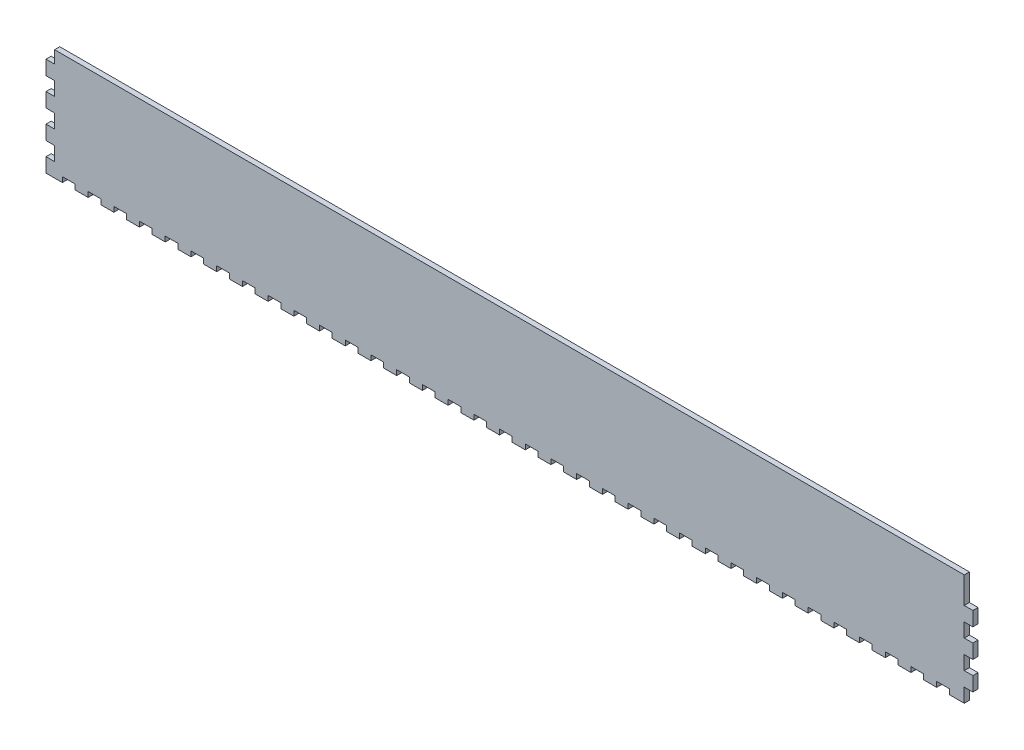
SolidWorks part; units mm, degrees
material "Perspex (TM) GS Acrylic Cast Sheet"
ref_plane "Front Plane" through (0, 0, 0) normal (0, 0, 1) x (1, 0, 0)
ref_plane "Top Plane" through (0, 0, 0) normal (0, 1, 0) x (1, 0, 0)
ref_plane "Right Plane" through (0, 0, 0) normal (1, 0, 0) x (0, 0, -1)
sketch "Sketch1" plane through (0, 0, 0) normal (0, 0, 1) x (1, 0, 0)
  line L0 (533.3602, 49.206) -> (533.3602, 64.6)
  line L413 (0, 0) -> (9.5185, 0)
  line L414 (9.5185, 3) -> (9.5185, 0)
  line L415 (9.5185, 3) -> (16.8869, 3)
  line L416 (16.8869, 3) -> (16.8869, 0)
  line L417 (16.8869, 0) -> (24.4554, 0)
  line L418 (24.4554, 3) -> (24.4554, 0)
  line L419 (24.4554, 3) -> (31.8238, 3)
  line L420 (31.8238, 3) -> (31.8238, 0)
  line L421 (31.8238, 0) -> (39.3923, 0)
  line L422 (39.3923, 3) -> (39.3923, 0)
  line L423 (39.3923, 3) -> (46.7607, 3)
  line L424 (46.7607, 3) -> (46.7607, 0)
  line L425 (46.7607, 0) -> (54.3292, 0)
  line L426 (54.3292, 3) -> (54.3292, 0)
  line L427 (54.3292, 3) -> (61.6976, 3)
  line L428 (61.6976, 3) -> (61.6976, 0)
  line L429 (61.6976, 0) -> (69.2661, 0)
  line L430 (69.2661, 3) -> (69.2661, 0)
  line L431 (69.2661, 3) -> (76.6345, 3)
  line L432 (76.6345, 3) -> (76.6345, 0)
  line L433 (76.6345, 0) -> (84.2031, 0)
  line L434 (84.2031, 3) -> (84.2031, 0)
  line L435 (84.2031, 3) -> (91.5713, 3)
  line L436 (91.5713, 3) -> (91.5713, 0)
  line L437 (91.5713, 0) -> (99.1398, 0)
  line L438 (99.1398, 3) -> (99.1398, 0)
  line L439 (99.1398, 3) -> (106.5082, 3)
  line L440 (106.5082, 3) -> (106.5082, 0)
  line L441 (106.5082, 0) -> (114.0767, 0)
  line L442 (114.0767, 3) -> (114.0767, 0)
  line L443 (114.0767, 3) -> (121.4452, 3)
  line L444 (121.4452, 3) -> (121.4452, 0)
  line L445 (121.4452, 0) -> (129.0137, 0)
  line L446 (129.0137, 3) -> (129.0137, 0)
  line L447 (129.0137, 3) -> (136.3822, 3)
  line L448 (136.3822, 3) -> (136.3822, 0)
  line L449 (136.3822, 0) -> (143.9507, 0)
  line L450 (143.9507, 3) -> (143.9507, 0)
  line L451 (143.9507, 3) -> (151.3191, 3)
  line L452 (151.3191, 3) -> (151.3191, 0)
  line L453 (151.3191, 0) -> (158.8876, 0)
  line L454 (158.8876, 3) -> (158.8876, 0)
  line L455 (158.8876, 3) -> (166.2561, 3)
  line L456 (166.2561, 3) -> (166.2561, 0)
  line L457 (166.2561, 0) -> (173.8242, 0)
  line L458 (173.8242, 3) -> (173.8242, 0)
  line L459 (173.8242, 3) -> (181.1927, 3)
  line L460 (181.1927, 3) -> (181.1927, 0)
  line L461 (181.1927, 0) -> (188.7612, 0)
  line L462 (188.7612, 3) -> (188.7612, 0)
  line L463 (188.7612, 3) -> (196.1297, 3)
  line L464 (196.1297, 3) -> (196.1297, 0)
  line L465 (196.1297, 0) -> (203.6981, 0)
  line L466 (203.6981, 3) -> (203.6981, 0)
  line L467 (203.6981, 3) -> (211.0666, 3)
  line L468 (211.0666, 3) -> (211.0666, 0)
  line L469 (211.0666, 0) -> (218.6351, 0)
  line L470 (218.6351, 3) -> (218.6351, 0)
  line L471 (218.6351, 3) -> (226.0036, 3)
  line L472 (226.0036, 3) -> (226.0036, 0)
  line L473 (226.0036, 0) -> (233.5721, 0)
  line L474 (233.5721, 3) -> (233.5721, 0)
  line L475 (233.5721, 3) -> (240.9406, 3)
  line L476 (240.9406, 3) -> (240.9406, 0)
  line L477 (240.9406, 0) -> (248.5091, 0)
  line L478 (248.5091, 3) -> (248.5091, 0)
  line L479 (248.5091, 3) -> (255.8775, 3)
  line L480 (255.8775, 3) -> (255.8775, 0)
  line L481 (255.8775, 0) -> (263.4457, 0)
  line L482 (263.4457, 3) -> (263.4457, 0)
  line L483 (263.4457, 3) -> (270.8141, 3)
  line L484 (270.8141, 3) -> (270.8141, 0)
  line L485 (270.8141, 0) -> (278.3826, 0)
  line L486 (278.3826, 3) -> (278.3826, 0)
  line L487 (278.3826, 3) -> (285.7511, 3)
  line L488 (285.7511, 3) -> (285.7511, 0)
  line L489 (285.7511, 0) -> (293.3196, 0)
  line L490 (293.3196, 3) -> (293.3196, 0)
  line L491 (293.3196, 3) -> (300.688, 3)
  line L492 (300.688, 3) -> (300.688, 0)
  line L493 (300.688, 0) -> (308.2565, 0)
  line L494 (308.2565, 3) -> (308.2565, 0)
  line L495 (308.2565, 3) -> (315.625, 3)
  line L496 (315.625, 3) -> (315.625, 0)
  line L497 (315.625, 0) -> (323.1935, 0)
  line L498 (323.1935, 3) -> (323.1935, 0)
  line L499 (323.1935, 3) -> (330.562, 3)
  line L500 (330.562, 3) -> (330.562, 0)
  line L501 (330.562, 0) -> (338.1301, 0)
  line L502 (338.1301, 3) -> (338.1301, 0)
  line L503 (338.1301, 3) -> (345.4986, 3)
  line L504 (345.4986, 3) -> (345.4986, 0)
  line L505 (345.4986, 0) -> (353.0671, 0)
  line L506 (353.0671, 3) -> (353.0671, 0)
  line L507 (353.0671, 3) -> (360.4356, 3)
  line L508 (360.4356, 3) -> (360.4356, 0)
  line L509 (360.4356, 0) -> (368.0041, 0)
  line L510 (368.0041, 3) -> (368.0041, 0)
  line L511 (368.0041, 3) -> (375.3725, 3)
  line L512 (375.3725, 3) -> (375.3725, 0)
  line L513 (375.3725, 0) -> (382.941, 0)
  line L514 (382.941, 3) -> (382.941, 0)
  line L515 (382.941, 3) -> (390.3095, 3)
  line L516 (390.3095, 3) -> (390.3095, 0)
  line L517 (390.3095, 0) -> (397.878, 0)
  line L518 (397.878, 3) -> (397.878, 0)
  line L519 (397.878, 3) -> (405.2464, 3)
  line L520 (405.2464, 3) -> (405.2464, 0)
  line L521 (405.2464, 0) -> (412.8149, 0)
  line L522 (412.8149, 3) -> (412.8149, 0)
  line L523 (412.8149, 3) -> (420.1834, 3)
  line L524 (420.1834, 3) -> (420.1834, 0)
  line L525 (420.1834, 0) -> (427.7515, 0)
  line L526 (427.7515, 3) -> (427.7515, 0)
  line L527 (427.7515, 3) -> (435.12, 3)
  line L528 (435.12, 3) -> (435.12, 0)
  line L529 (435.12, 0) -> (442.6885, 0)
  line L530 (442.6885, 3) -> (442.6885, 0)
  line L531 (442.6885, 3) -> (450.057, 3)
  line L532 (450.057, 3) -> (450.057, 0)
  line L533 (450.057, 0) -> (457.6255, 0)
  line L534 (457.6255, 3) -> (457.6255, 0)
  line L535 (457.6255, 3) -> (464.994, 3)
  line L536 (464.994, 3) -> (464.994, 0)
  line L537 (464.994, 0) -> (472.5625, 0)
  line L538 (472.5625, 3) -> (472.5625, 0)
  line L539 (472.5625, 3) -> (479.9309, 3)
  line L540 (479.9309, 3) -> (479.9309, 0)
  line L541 (479.9309, 0) -> (487.4994, 0)
  line L542 (487.4994, 3) -> (487.4994, 0)
  line L543 (487.4994, 3) -> (494.8679, 3)
  line L544 (494.8679, 3) -> (494.8679, 0)
  line L545 (494.8679, 0) -> (502.4364, 0)
  line L546 (502.4364, 3) -> (502.4364, 0)
  line L547 (502.4364, 3) -> (509.8045, 3)
  line L548 (509.8045, 3) -> (509.8045, 0)
  line L549 (509.8045, 0) -> (517.373, 0)
  line L550 (517.373, 3) -> (517.373, 0)
  line L551 (517.373, 3) -> (524.7414, 3)
  line L552 (524.7414, 3) -> (524.7414, 0)
  line L553 (524.7414, 0) -> (533.3602, 0)
  line L554 (0, 0) -> (0, 8.3)
  line L555 (5, 8.3) -> (0, 8.3)
  line L556 (5, 8.3) -> (5, 16.38)
  line L557 (5, 16.38) -> (0, 16.38)
  line L558 (0, 16.38) -> (0, 24.68)
  line L559 (5, 24.68) -> (0, 24.68)
  line L560 (5, 24.68) -> (5, 32.76)
  line L561 (5, 32.76) -> (0, 32.76)
  line L562 (0, 32.76) -> (0, 41.06)
  line L563 (533.3602, 0) -> (533.3602, 8.1458)
  line L564 (538.3599, 8.1458) -> (533.3602, 8.1458)
  line L565 (538.3599, 8.1458) -> (538.3599, 16.4351)
  line L566 (538.3599, 16.4351) -> (533.3602, 16.4351)
  line L567 (533.3602, 16.4351) -> (533.3602, 24.5243)
  line L568 (538.3599, 24.5243) -> (533.3602, 24.5243)
  line L569 (538.3599, 24.5243) -> (538.3599, 32.8136)
  line L570 (538.3599, 32.8136) -> (533.3602, 32.8136)
  line L571 (533.3602, 32.8136) -> (533.3602, 40.9167)
  line L572 (533.3602, 64.6) -> (5, 64.6)
  line L573 (5, 41.06) -> (0, 41.06)
  line L574 (5, 41.06) -> (5, 49.0343)
  line L575 (5, 49.0343) -> (0, 49.0343)
  line L576 (0, 49.0343) -> (0, 57.3343)
  line L577 (5, 57.3343) -> (0, 57.3343)
  line L578 (5, 57.3343) -> (5, 64.6)
  line L579 (538.3599, 40.9167) -> (533.3602, 40.9167)
  line L580 (538.3599, 40.9167) -> (538.3599, 49.206)
  line L581 (538.3599, 49.206) -> (533.3602, 49.206)
  dimension "D1" = 64.6
  dimension "D2" = 7.2657
  dimension "D3" = 8.3
  dimension "D4" = 8.08
  dimension "D5" = 8.08
extrude "Boss-Extrude1" add sketch "Sketch1" along normal blind 3
sketch "Sketch2" [suppressed] plane through (0, 0, 3) normal (0, 0, 1) x (1, 0, 0)
  line L1 (155.1929, 42.1264) -> (155.1929, 45.3454)
  line L2 (153.3481, 41.1853) -> (155.1929, 42.1264)
  line L3 (151.5033, 40.2441) -> (153.3481, 41.1853)
  line L4 (151.5033, 44.4043) -> (151.5033, 40.2441)
  line L5 (151.5033, 48.5644) -> (151.5033, 44.4043)
  line L6 (153.3481, 48.5644) -> (151.5033, 48.5644)
  line L7 (155.1929, 48.5644) -> (153.3481, 48.5644)
  line L8 (155.1929, 45.3454) -> (155.1929, 48.5644)
  line L9 (149.6585, 37.4854) -> (149.6585, 43.9473)
  line L10 (153.3481, 39.3405) -> (149.6585, 37.4854)
  line L11 (157.0377, 41.1956) -> (153.3481, 39.3405)
  line L12 (157.0377, 45.8024) -> (157.0377, 41.1956)
  line L13 (157.0377, 50.4092) -> (157.0377, 45.8024)
  line L14 (153.3481, 50.4092) -> (157.0377, 50.4092)
  line L15 (149.6585, 50.4092) -> (153.3481, 50.4092)
  line L16 (149.6585, 43.9473) -> (149.6585, 50.4092)
  line L17 (108.6121, 36.5921) -> (108.6121, 42.5782)
  line L18 (106.7673, 35.6509) -> (108.6121, 36.5921)
  line L19 (104.9225, 34.7098) -> (106.7673, 35.6509)
  line L20 (104.9225, 41.6371) -> (104.9225, 34.7098)
  line L21 (104.9225, 48.5644) -> (104.9225, 41.6371)
  line L22 (106.7673, 48.5644) -> (104.9225, 48.5644)
  line L23 (108.6121, 48.5644) -> (106.7673, 48.5644)
  line L24 (108.6121, 42.5782) -> (108.6121, 48.5644)
  line L25 (110.4569, 35.7343) -> (107.0196, 33.8478)
  line L26 (110.4569, 43.0717) -> (110.4569, 35.7343)
  line L27 (110.4569, 50.4092) -> (110.4569, 43.0717)
  line L28 (106.7673, 50.4092) -> (110.4569, 50.4092)
  line L29 (103.0777, 50.4092) -> (106.7673, 50.4092)
  line L30 (103.0777, 41.1853) -> (103.0777, 50.4092)
  line L31 (396.8595, 27.8106) -> (396.8595, 38.1875)
  line L32 (395.0147, 27.8106) -> (396.8595, 27.8106)
  line L33 (393.1699, 27.8106) -> (395.0147, 27.8106)
  line L34 (393.1699, 38.1875) -> (393.1699, 27.8106)
  line L35 (393.1699, 48.5644) -> (393.1699, 38.1875)
  line L36 (395.0147, 48.5644) -> (393.1699, 48.5644)
  line L37 (396.8595, 48.5644) -> (395.0147, 48.5644)
  line L38 (396.8595, 38.1875) -> (396.8595, 48.5644)
  line L39 (391.3251, 25.9658) -> (391.3251, 38.1875)
  line L40 (395.0147, 25.9658) -> (391.3251, 25.9658)
  line L41 (398.7042, 25.9658) -> (395.0147, 25.9658)
  line L42 (398.7042, 38.1875) -> (398.7042, 25.9658)
  line L43 (398.7042, 50.4092) -> (398.7042, 38.1875)
  line L44 (395.0147, 50.4092) -> (398.7042, 50.4092)
  line L45 (391.3251, 50.4092) -> (395.0147, 50.4092)
  line L46 (391.3251, 38.1875) -> (391.3251, 50.4092)
  line L47 (356.7354, 27.8106) -> (356.7354, 38.1875)
  line L48 (354.8907, 27.8106) -> (356.7354, 27.8106)
  line L49 (353.0459, 27.8106) -> (354.8907, 27.8106)
  line L50 (353.0459, 38.1875) -> (353.0459, 27.8106)
  line L51 (353.0459, 48.5644) -> (353.0459, 38.1875)
  line L52 (354.8907, 48.5644) -> (353.0459, 48.5644)
  line L53 (356.7354, 48.5644) -> (354.8907, 48.5644)
  line L54 (356.7354, 38.1875) -> (356.7354, 48.5644)
  line L55 (351.2011, 25.9658) -> (351.2011, 38.1875)
  line L56 (354.8907, 25.9658) -> (351.2011, 25.9658)
  line L57 (358.5802, 25.9658) -> (354.8907, 25.9658)
  line L58 (358.5802, 38.1875) -> (358.5802, 25.9658)
  line L59 (358.5802, 50.4092) -> (358.5802, 38.1875)
  line L60 (354.8907, 50.4092) -> (358.5802, 50.4092)
  line L61 (351.2011, 50.4092) -> (354.8907, 50.4092)
  line L62 (351.2011, 38.1875) -> (351.2011, 50.4092)
  line L63 (149.6585, 25.9658) -> (149.6585, 29.6605)
  line L64 (153.3481, 25.9658) -> (149.6585, 25.9658)
  line L65 (157.0377, 25.9658) -> (153.3481, 25.9658)
  line L66 (157.0377, 27.8054) -> (157.0377, 25.9658)
  line L67 (149.6585, 33.3552) -> (153.3481, 31.5002)
  line L68 (149.6585, 29.6605) -> (149.6585, 33.3552)
  line L69 (235.7413, 17.4806) -> (235.7411, 17.4806)
  line L70 (237.3694, 50.4092) -> (237.2123, 32.6759)
  line L71 (234.5605, 50.4092) -> (237.3694, 50.4092)
  line L72 (231.7515, 50.4092) -> (234.5605, 50.4092)
  line L73 (231.7515, 52.254) -> (231.7515, 50.4092)
  line L74 (231.7515, 54.0988) -> (231.7515, 52.254)
  line L75 (239.1306, 54.0988) -> (231.7515, 54.0988)
  line L76 (246.5098, 54.0988) -> (239.1306, 54.0988)
  line L77 (246.5098, 52.254) -> (246.5098, 54.0988)
  line L78 (246.5098, 50.4092) -> (246.5098, 52.254)
  line L79 (243.6972, 50.4092) -> (246.5098, 50.4092)
  line L80 (240.8845, 50.4092) -> (243.6972, 50.4092)
  line L81 (241.0453, 32.676) -> (240.8845, 50.4092)
  line L82 (242.8201, 48.5644) -> (242.817, 34.3826)
  line L83 (245.5873, 48.5644) -> (242.8201, 48.5644)
  line L84 (248.3544, 48.5644) -> (245.5873, 48.5644)
  line L85 (248.3544, 52.254) -> (248.3544, 48.5644)
  line L86 (248.3544, 55.9435) -> (248.3544, 52.254)
  line L87 (239.1305, 55.9435) -> (248.3544, 55.9435)
  line L88 (229.9066, 55.9435) -> (239.1305, 55.9435)
  line L89 (229.9066, 52.254) -> (229.9066, 55.9435)
  line L90 (229.9066, 48.5644) -> (229.9066, 52.254)
  line L91 (232.6738, 48.5644) -> (229.9066, 48.5644)
  line L92 (235.4409, 48.5644) -> (232.6738, 48.5644)
  line L93 (235.4409, 34.7981) -> (235.4409, 48.5644)
  line L94 (108.5361, 23.064) -> (106.9443, 23.8231)
  line L95 (108.8601, 18.743) -> (108.5361, 23.064)
  line L96 (103.0777, 27.8734) -> (106.7669, 25.8819)
  line L97 (103.0777, 24.4526) -> (103.0777, 27.8734)
  line L98 (99.4734, 54.0988) -> (99.2858, 34.8438)
  line L99 (106.8099, 54.0988) -> (99.4734, 54.0988)
  line L100 (114.1464, 54.0988) -> (106.8099, 54.0988)
  line L101 (114.1464, 43.5902) -> (114.1464, 54.0988)
  line L102 (114.1464, 33.0817) -> (114.1464, 43.5902)
  line L103 (111.0943, 31.5766) -> (114.1464, 33.0817)
  line L104 (113.9159, 26.6576) -> (111.2929, 28.0508)
  line L105 (114.2545, 21.5845) -> (113.9159, 26.6576)
  line L106 (115.9912, 27.6268) -> (115.9456, 22.9914)
  line L107 (113.8021, 28.6904) -> (115.9912, 27.6268)
  line L108 (111.613, 29.7539) -> (113.8021, 28.6904)
  line L109 (113.8021, 30.8665) -> (111.613, 29.7539)
  line L110 (115.9912, 31.979) -> (113.8021, 30.8665)
  line L111 (115.9912, 43.9613) -> (115.9912, 31.979)
  line L112 (115.9912, 55.9435) -> (115.9912, 43.9613)
  line L113 (106.7673, 55.9435) -> (115.9912, 55.9435)
  line L114 (97.5434, 55.9435) -> (106.7673, 55.9435)
  line L115 (97.5434, 38.2571) -> (97.5434, 55.9435)
  line L116 (333.9811, 16.5113) -> (333.9812, 16.5113)
  line L117 (329.7555, 31.7308) -> (329.4691, 24.8128)
  line L118 (331.6999, 25.9658) -> (329.7555, 31.7308)
  line L119 (317.0725, 55.9435) -> (317.0269, 36.6886)
  line L120 (313.383, 55.9435) -> (317.0725, 55.9435)
  line L121 (309.6934, 55.9435) -> (313.383, 55.9435)
  line L122 (309.6934, 44.6442) -> (309.6934, 55.9435)
  line L123 (309.6934, 33.345) -> (309.6934, 44.6442)
  line L124 (307.8486, 33.345) -> (309.6934, 33.345)
  line L125 (306.0038, 33.345) -> (307.8486, 33.345)
  line L126 (306.0038, 44.6442) -> (306.0038, 33.345)
  line L127 (306.0038, 55.9435) -> (306.0038, 44.6442)
  line L128 (302.3143, 55.9435) -> (306.0038, 55.9435)
  line L129 (298.6247, 55.9435) -> (302.3143, 55.9435)
  line L130 (298.6275, 38.5334) -> (298.6247, 55.9435)
  line L131 (300.5485, 54.0988) -> (300.3487, 35.0744)
  line L132 (302.3538, 54.0988) -> (300.5485, 54.0988)
  line L133 (304.1591, 54.0988) -> (302.3538, 54.0988)
  line L134 (304.1591, 42.7995) -> (304.1591, 54.0988)
  line L135 (304.1591, 31.5002) -> (304.1591, 42.7995)
  line L136 (307.8487, 31.5002) -> (304.1591, 31.5002)
  line L137 (311.5382, 31.5002) -> (307.8487, 31.5002)
  line L138 (311.5382, 42.7995) -> (311.5382, 31.5002)
  line L139 (311.5382, 54.0988) -> (311.5382, 42.7995)
  line L140 (313.3379, 54.0988) -> (311.5382, 54.0988)
  line L141 (315.1375, 54.0988) -> (313.3379, 54.0988)
  line L142 (315.3524, 34.3826) -> (315.1375, 54.0988)
  line L143 (427.7596, 38.8793) -> (427.714, 27.2341)
  line L144 (424.07, 38.8793) -> (427.7596, 38.8793)
  line L145 (420.3805, 38.8793) -> (424.07, 38.8793)
  line L146 (420.3805, 33.345) -> (420.3805, 38.8793)
  line L147 (420.3805, 27.8106) -> (420.3805, 33.345)
  line L148 (418.5357, 27.8106) -> (420.3805, 27.8106)
  line L149 (416.6909, 27.8106) -> (418.5357, 27.8106)
  line L150 (416.6909, 38.1875) -> (416.6909, 27.8106)
  line L151 (416.6909, 48.5644) -> (416.6909, 38.1875)
  line L152 (418.5357, 48.5644) -> (416.6909, 48.5644)
  line L153 (420.3805, 48.5644) -> (418.5357, 48.5644)
  line L154 (420.3805, 45.7972) -> (420.3805, 48.5644)
  line L155 (420.3805, 43.0301) -> (420.3805, 45.7972)
  line L156 (424.07, 43.0301) -> (420.3805, 43.0301)
  line L157 (427.7596, 43.0301) -> (424.07, 43.0301)
  line L158 (427.7596, 49.4868) -> (427.7596, 43.0301)
  line L159 (427.7596, 55.9435) -> (427.7596, 49.4868)
  line L160 (418.5357, 55.9435) -> (427.7596, 55.9435)
  line L161 (409.3118, 55.9435) -> (418.5357, 55.9435)
  line L162 (409.3118, 38.7183) -> (409.3118, 55.9435)
  line L163 (411.2363, 54.0988) -> (411.0551, 35.305)
  line L164 (418.5755, 54.0988) -> (411.2363, 54.0988)
  line L165 (425.9148, 54.0988) -> (418.5755, 54.0988)
  line L166 (425.9148, 49.4868) -> (425.9148, 54.0988)
  line L167 (425.9148, 44.8748) -> (425.9148, 49.4868)
  line L168 (424.07, 44.8748) -> (425.9148, 44.8748)
  line L169 (422.2252, 44.8748) -> (424.07, 44.8748)
  line L170 (422.2252, 47.642) -> (422.2252, 44.8748)
  line L171 (422.2252, 50.4092) -> (422.2252, 47.642)
  line L172 (418.5357, 50.4092) -> (422.2252, 50.4092)
  line L173 (414.8461, 50.4092) -> (418.5357, 50.4092)
  line L174 (414.8461, 38.1875) -> (414.8461, 50.4092)
  line L175 (414.8461, 25.9658) -> (414.8461, 38.1875)
  line L176 (418.5357, 25.9658) -> (414.8461, 25.9658)
  line L177 (422.2252, 25.9658) -> (418.5357, 25.9658)
  line L178 (422.2252, 31.5002) -> (422.2252, 25.9658)
  line L179 (422.2252, 37.0345) -> (422.2252, 31.5002)
  line L180 (424.0113, 37.0345) -> (422.2252, 37.0345)
  line L181 (425.7975, 37.0345) -> (424.0113, 37.0345)
  line L182 (426.0611, 25.1587) -> (425.7975, 37.0345)
  line L183 (369.4931, 13.7313) -> (369.493, 13.7313)
  line L184 (371.1129, 54.0988) -> (370.9311, 33.2296)
  line L185 (372.9175, 54.0988) -> (371.1129, 54.0988)
  line L186 (374.7222, 54.0988) -> (372.9175, 54.0988)
  line L187 (374.7222, 40.0323) -> (374.7222, 54.0988)
  line L188 (374.7222, 25.9658) -> (374.7222, 40.0323)
  line L189 (377.4237, 25.9658) -> (374.7222, 25.9658)
  line L190 (380.1253, 25.9658) -> (377.4237, 25.9658)
  line L191 (380.4506, 20.7774) -> (380.1253, 25.9658)
  line L192 (382.1012, 27.8106) -> (382.0981, 24.4669)
  line L193 (379.334, 27.8106) -> (382.1012, 27.8106)
  line L194 (376.5668, 27.8106) -> (379.334, 27.8106)
  line L195 (376.5668, 41.8771) -> (376.5668, 27.8106)
  line L196 (376.5668, 55.9435) -> (376.5668, 41.8771)
  line L197 (372.8773, 55.9435) -> (376.5668, 55.9435)
  line L198 (369.1877, 55.9435) -> (372.8773, 55.9435)
  line L199 (369.1877, 36.6429) -> (369.1877, 55.9435)
  line L200 (294.0128, 33.345) -> (293.9672, 24.2363)
  line L201 (290.3232, 33.345) -> (294.0128, 33.345)
  line L202 (286.6337, 33.345) -> (290.3232, 33.345)
  line L203 (286.6337, 30.5778) -> (286.6337, 33.345)
  line L204 (286.6337, 27.8106) -> (286.6337, 30.5778)
  line L205 (284.7889, 27.8106) -> (286.6337, 27.8106)
  line L206 (282.9441, 27.8106) -> (284.7889, 27.8106)
  line L207 (282.9441, 38.1875) -> (282.9441, 27.8106)
  line L208 (282.9441, 48.5644) -> (282.9441, 38.1875)
  line L209 (284.7889, 48.5644) -> (282.9441, 48.5644)
  line L210 (286.6337, 48.5644) -> (284.7889, 48.5644)
  line L211 (286.6337, 45.7972) -> (286.6337, 48.5644)
  line L212 (286.6337, 43.0301) -> (286.6337, 45.7972)
  line L213 (290.3232, 43.0301) -> (286.6337, 43.0301)
  line L214 (294.0128, 43.0301) -> (290.3232, 43.0301)
  line L215 (294.0128, 49.4868) -> (294.0128, 43.0301)
  line L216 (294.0128, 55.9435) -> (294.0128, 49.4868)
  line L217 (284.7889, 55.9435) -> (294.0128, 55.9435)
  line L218 (275.565, 55.9435) -> (284.7889, 55.9435)
  line L219 (275.565, 38.4877) -> (275.565, 55.9435)
  line L220 (277.4958, 54.0988) -> (277.3072, 35.0744)
  line L221 (284.8319, 54.0988) -> (277.4958, 54.0988)
  line L222 (292.168, 54.0988) -> (284.8319, 54.0988)
  line L223 (292.168, 49.4868) -> (292.168, 54.0988)
  line L224 (292.168, 44.8748) -> (292.168, 49.4868)
  line L225 (290.3232, 44.8748) -> (292.168, 44.8748)
  line L226 (288.4785, 44.8748) -> (290.3232, 44.8748)
  line L227 (288.4785, 47.642) -> (288.4785, 44.8748)
  line L228 (288.4785, 50.4092) -> (288.4785, 47.642)
  line L229 (284.7889, 50.4092) -> (288.4785, 50.4092)
  line L230 (281.0993, 50.4092) -> (284.7889, 50.4092)
  line L231 (281.0993, 38.1875) -> (281.0993, 50.4092)
  line L232 (281.0993, 25.9658) -> (281.0993, 38.1875)
  line L233 (284.7889, 25.9658) -> (281.0993, 25.9658)
  line L234 (288.4785, 25.9658) -> (284.7889, 25.9658)
  line L235 (288.4785, 28.733) -> (288.4785, 25.9658)
  line L236 (288.4785, 31.5002) -> (288.4785, 28.733)
  line L237 (290.2572, 31.5002) -> (288.4785, 31.5002)
  line L238 (292.036, 31.5002) -> (290.2572, 31.5002)
  line L239 (292.321, 22.1609) -> (292.036, 31.5002)
  line L240 (191.0103, 13.7313) -> (191.0102, 13.7313)
  line L241 (192.6301, 54.0988) -> (192.4483, 33.2296)
  line L242 (194.4348, 54.0988) -> (192.6301, 54.0988)
  line L243 (196.2394, 54.0988) -> (194.4348, 54.0988)
  line L244 (196.2394, 40.0323) -> (196.2394, 54.0988)
  line L245 (196.2394, 25.9658) -> (196.2394, 40.0323)
  line L246 (198.9409, 25.9658) -> (196.2394, 25.9658)
  line L247 (201.6425, 25.9658) -> (198.9409, 25.9658)
  line L248 (201.9678, 20.7774) -> (201.6425, 25.9658)
  line L249 (203.6184, 27.8106) -> (203.6153, 24.4669)
  line L250 (200.8513, 27.8106) -> (203.6184, 27.8106)
  line L251 (198.0841, 27.8106) -> (200.8513, 27.8106)
  line L252 (198.0841, 41.8771) -> (198.0841, 27.8106)
  line L253 (198.0841, 55.9435) -> (198.0841, 41.8771)
  line L254 (194.3945, 55.9435) -> (198.0841, 55.9435)
  line L255 (190.7049, 55.9435) -> (194.3945, 55.9435)
  line L256 (190.7049, 36.6429) -> (190.7049, 55.9435)
  line L257 (146.0492, 54.0988) -> (145.8674, 33.2296)
  line L258 (153.3882, 54.0988) -> (146.0492, 54.0988)
  line L259 (160.7272, 54.0988) -> (153.3882, 54.0988)
  line L260 (160.7272, 46.3574) -> (160.7272, 54.0988)
  line L261 (160.7272, 38.6161) -> (160.7272, 46.3574)
  line L262 (157.6751, 37.111) -> (160.7272, 38.6161)
  line L263 (160.4966, 32.192) -> (157.8736, 33.5851)
  line L264 (160.7824, 24.5738) -> (160.4966, 32.192)
  line L265 (162.572, 33.1611) -> (162.5264, 25.9892)
  line L266 (160.396, 34.2183) -> (162.572, 33.1611)
  line L267 (158.22, 35.2755) -> (160.396, 34.2183)
  line L268 (160.0501, 36.3833) -> (158.22, 35.2755)
  line L269 (162.572, 55.9435) -> (162.572, 46.7196)
  line L270 (153.3481, 55.9435) -> (162.572, 55.9435)
  line L271 (144.1242, 55.9435) -> (153.3481, 55.9435)
  line L272 (144.1242, 36.6429) -> (144.1242, 55.9435)
  line L273 (270.953, 27.8106) -> (270.9074, 21.2386)
  line L274 (265.4187, 27.8106) -> (270.953, 27.8106)
  line L275 (259.8843, 27.8106) -> (265.4187, 27.8106)
  line L276 (259.8843, 29.6554) -> (259.8843, 27.8106)
  line L277 (259.8843, 31.5002) -> (259.8843, 29.6554)
  line L278 (265.4187, 31.5002) -> (259.8843, 31.5002)
  line L279 (270.953, 31.5002) -> (265.4187, 31.5002)
  line L280 (270.953, 35.1897) -> (270.953, 31.5002)
  line L281 (270.953, 38.8793) -> (270.953, 35.1897)
  line L282 (265.4187, 38.8793) -> (270.953, 38.8793)
  line L283 (259.8843, 38.8793) -> (265.4187, 38.8793)
  line L284 (259.8843, 43.7218) -> (259.8843, 38.8793)
  line L285 (259.8843, 48.5644) -> (259.8843, 43.7218)
  line L286 (261.7291, 48.5644) -> (259.8843, 48.5644)
  line L287 (263.5739, 48.5644) -> (261.7291, 48.5644)
  line L288 (263.5739, 45.7972) -> (263.5739, 48.5644)
  line L289 (263.5739, 43.0301) -> (263.5739, 45.7972)
  line L290 (267.2634, 43.0301) -> (263.5739, 43.0301)
  line L291 (270.953, 43.0301) -> (267.2634, 43.0301)
  line L292 (270.953, 49.4868) -> (270.953, 43.0301)
  line L293 (270.953, 55.9435) -> (270.953, 49.4868)
  line L294 (261.7291, 55.9435) -> (270.953, 55.9435)
  line L295 (252.5052, 55.9435) -> (261.7291, 55.9435)
  line L296 (252.5052, 37.7959) -> (252.5052, 55.9435)
  line L297 (254.4337, 54.0988) -> (254.2478, 34.3826)
  line L298 (261.771, 54.0988) -> (254.4337, 54.0988)
  line L299 (269.1082, 54.0988) -> (261.771, 54.0988)
  line L300 (269.1082, 49.4868) -> (269.1082, 54.0988)
  line L301 (269.1082, 44.8748) -> (269.1082, 49.4868)
  line L302 (267.2634, 44.8748) -> (269.1082, 44.8748)
  line L303 (265.4187, 44.8748) -> (267.2634, 44.8748)
  line L304 (265.4187, 47.642) -> (265.4187, 44.8748)
  line L305 (265.4187, 50.4092) -> (265.4187, 47.642)
  line L306 (261.7291, 50.4092) -> (265.4187, 50.4092)
  line L307 (258.0395, 50.4092) -> (261.7291, 50.4092)
  line L308 (258.0395, 43.7218) -> (258.0395, 50.4092)
  line L309 (258.0395, 37.0345) -> (258.0395, 43.7218)
  line L310 (263.5739, 37.0345) -> (258.0395, 37.0345)
  line L311 (269.1082, 37.0345) -> (263.5739, 37.0345)
  line L312 (269.1082, 35.1897) -> (269.1082, 37.0345)
  line L313 (269.1082, 33.345) -> (269.1082, 35.1897)
  line L314 (263.5739, 33.345) -> (269.1082, 33.345)
  line L315 (258.0395, 33.345) -> (263.5739, 33.345)
  line L316 (258.0395, 29.6554) -> (258.0395, 33.345)
  line L317 (258.0395, 25.9658) -> (258.0395, 29.6554)
  line L318 (263.5022, 25.9658) -> (258.0395, 25.9658)
  line L319 (268.9648, 25.9658) -> (263.5022, 25.9658)
  line L320 (269.276, 19.1632) -> (268.9648, 25.9658)
  line L321 (186.093, 27.8106) -> (186.0474, 21.2386)
  line L322 (180.5586, 27.8106) -> (186.093, 27.8106)
  line L323 (175.0243, 27.8106) -> (180.5586, 27.8106)
  line L324 (175.0243, 29.6554) -> (175.0243, 27.8106)
  line L325 (175.0243, 31.5002) -> (175.0243, 29.6554)
  line L326 (180.5586, 31.5002) -> (175.0243, 31.5002)
  line L327 (186.093, 31.5002) -> (180.5586, 31.5002)
  line L328 (186.093, 35.1897) -> (186.093, 31.5002)
  line L329 (186.093, 38.8793) -> (186.093, 35.1897)
  line L330 (180.5586, 38.8793) -> (186.093, 38.8793)
  line L331 (175.0243, 38.8793) -> (180.5586, 38.8793)
  line L332 (175.0243, 43.7218) -> (175.0243, 38.8793)
  line L333 (175.0243, 48.5644) -> (175.0243, 43.7218)
  line L334 (176.8691, 48.5644) -> (175.0243, 48.5644)
  line L335 (178.7139, 48.5644) -> (176.8691, 48.5644)
  line L336 (178.7139, 45.7972) -> (178.7139, 48.5644)
  line L337 (178.7139, 43.0301) -> (178.7139, 45.7972)
  line L338 (182.4034, 43.0301) -> (178.7139, 43.0301)
  line L339 (186.093, 43.0301) -> (182.4034, 43.0301)
  line L340 (186.093, 49.4868) -> (186.093, 43.0301)
  line L341 (186.093, 55.9435) -> (186.093, 49.4868)
  line L342 (176.8691, 55.9435) -> (186.093, 55.9435)
  line L343 (167.6452, 55.9435) -> (176.8691, 55.9435)
  line L344 (167.6452, 37.7959) -> (167.6452, 55.9435)
  line L345 (169.5737, 54.0988) -> (169.3878, 34.3826)
  line L346 (176.911, 54.0988) -> (169.5737, 54.0988)
  line L347 (184.2482, 54.0988) -> (176.911, 54.0988)
  line L348 (184.2482, 49.4868) -> (184.2482, 54.0988)
  line L349 (184.2482, 44.8748) -> (184.2482, 49.4868)
  line L350 (182.4034, 44.8748) -> (184.2482, 44.8748)
  line L351 (180.5586, 44.8748) -> (182.4034, 44.8748)
  line L352 (180.5586, 47.642) -> (180.5586, 44.8748)
  line L353 (180.5586, 50.4092) -> (180.5586, 47.642)
  line L354 (176.8691, 50.4092) -> (180.5586, 50.4092)
  line L355 (173.1795, 50.4092) -> (176.8691, 50.4092)
  line L356 (173.1795, 43.7218) -> (173.1795, 50.4092)
  line L357 (173.1795, 37.0345) -> (173.1795, 43.7218)
  line L358 (178.7139, 37.0345) -> (173.1795, 37.0345)
  line L359 (184.2482, 37.0345) -> (178.7139, 37.0345)
  line L360 (184.2482, 35.1897) -> (184.2482, 37.0345)
  line L361 (184.2482, 33.345) -> (184.2482, 35.1897)
  line L362 (178.7139, 33.345) -> (184.2482, 33.345)
  line L363 (173.1795, 33.345) -> (178.7139, 33.345)
  line L364 (173.1795, 29.6554) -> (173.1795, 33.345)
  line L365 (173.1795, 25.9658) -> (173.1795, 29.6554)
  line L366 (178.6421, 25.9658) -> (173.1795, 25.9658)
  line L367 (184.1048, 25.9658) -> (178.6421, 25.9658)
  line L368 (184.416, 19.1632) -> (184.1048, 25.9658)
  line L369 (139.5122, 27.8106) -> (139.4666, 21.2386)
  line L370 (133.9779, 27.8106) -> (139.5122, 27.8106)
  line L371 (128.4435, 27.8106) -> (133.9779, 27.8106)
  line L372 (128.4435, 29.6554) -> (128.4435, 27.8106)
  line L373 (128.4435, 31.5002) -> (128.4435, 29.6554)
  line L374 (133.9779, 31.5002) -> (128.4435, 31.5002)
  line L375 (139.5122, 31.5002) -> (133.9779, 31.5002)
  line L376 (139.5122, 35.1897) -> (139.5122, 31.5002)
  line L377 (139.5122, 38.8793) -> (139.5122, 35.1897)
  line L378 (133.9779, 38.8793) -> (139.5122, 38.8793)
  line L379 (128.4435, 38.8793) -> (133.9779, 38.8793)
  line L380 (128.4435, 43.7218) -> (128.4435, 38.8793)
  line L381 (128.4435, 48.5644) -> (128.4435, 43.7218)
  line L382 (130.2883, 48.5644) -> (128.4435, 48.5644)
  line L383 (132.1331, 48.5644) -> (130.2883, 48.5644)
  line L384 (132.1331, 45.7972) -> (132.1331, 48.5644)
  line L385 (132.1331, 43.0301) -> (132.1331, 45.7972)
  line L386 (135.8227, 43.0301) -> (132.1331, 43.0301)
  line L387 (139.5122, 43.0301) -> (135.8227, 43.0301)
  line L388 (139.5122, 49.4868) -> (139.5122, 43.0301)
  line L389 (139.5122, 55.9435) -> (139.5122, 49.4868)
  line L390 (130.2883, 55.9435) -> (139.5122, 55.9435)
  line L391 (121.0644, 55.9435) -> (130.2883, 55.9435)
  line L392 (121.0644, 37.7959) -> (121.0644, 55.9435)
  line L393 (122.9929, 54.0988) -> (122.807, 34.3826)
  line L394 (130.3302, 54.0988) -> (122.9929, 54.0988)
  line L395 (137.6674, 54.0988) -> (130.3302, 54.0988)
  line L396 (137.6674, 49.4868) -> (137.6674, 54.0988)
  line L397 (137.6674, 44.8748) -> (137.6674, 49.4868)
  line L398 (135.8227, 44.8748) -> (137.6674, 44.8748)
  line L399 (133.9779, 44.8748) -> (135.8227, 44.8748)
  line L400 (133.9779, 47.642) -> (133.9779, 44.8748)
  line L401 (133.9779, 50.4092) -> (133.9779, 47.642)
  line L402 (130.2883, 50.4092) -> (133.9779, 50.4092)
  line L403 (126.5987, 50.4092) -> (130.2883, 50.4092)
  line L404 (126.5987, 43.7218) -> (126.5987, 50.4092)
  line L405 (126.5987, 37.0345) -> (126.5987, 43.7218)
  line L406 (132.1331, 37.0345) -> (126.5987, 37.0345)
  line L407 (137.6674, 37.0345) -> (132.1331, 37.0345)
  line L408 (137.6674, 35.1897) -> (137.6674, 37.0345)
  line L409 (137.6674, 33.345) -> (137.6674, 35.1897)
  line L410 (132.1331, 33.345) -> (137.6674, 33.345)
  line L411 (126.5987, 33.345) -> (132.1331, 33.345)
  line L412 (126.5987, 29.6554) -> (126.5987, 33.345)
  line L413 (126.5987, 25.9658) -> (126.5987, 29.6554)
  line L414 (132.0614, 25.9658) -> (126.5987, 25.9658)
  line L415 (137.524, 25.9658) -> (132.0614, 25.9658)
  line L416 (137.8352, 19.1632) -> (137.524, 25.9658)
  line L417 (386.0961, 12.3477) -> (386.096, 12.3477)
  line L418 (387.7139, 54.0988) -> (387.5345, 32.5379)
  line L419 (395.0109, 54.0988) -> (387.7139, 54.0988)
  line L420 (402.3079, 54.0988) -> (395.0109, 54.0988)
  line L421 (402.4965, 35.0744) -> (402.3079, 54.0988)
  line L422 (404.2386, 55.9435) -> (404.2355, 38.0722)
  line L423 (395.0147, 55.9435) -> (404.2386, 55.9435)
  line L424 (385.7908, 55.9435) -> (395.0147, 55.9435)
  line L425 (385.7908, 35.9511) -> (385.7908, 55.9435)
  line L426 (345.9721, 12.3477) -> (345.972, 12.3477)
  line L427 (347.5899, 54.0988) -> (347.4104, 32.5379)
  line L428 (354.8869, 54.0988) -> (347.5899, 54.0988)
  line L429 (362.1839, 54.0988) -> (354.8869, 54.0988)
  line L430 (362.3724, 35.0744) -> (362.1839, 54.0988)
  line L431 (364.1146, 55.9435) -> (364.1115, 38.0722)
  line L432 (354.8907, 55.9435) -> (364.1146, 55.9435)
  line L433 (345.6667, 55.9435) -> (354.8907, 55.9435)
  line L434 (345.6667, 35.9511) -> (345.6667, 55.9435)
  line L435 (304.4594, 12.4075) -> (304.4593, 12.4075)
  line L436 (306.1436, 25.9658) -> (305.881, 17.8405)
  line L437 (307.8593, 25.9658) -> (306.1436, 25.9658)
  line L438 (309.5749, 25.9658) -> (307.8593, 25.9658)
  line L439 (309.9036, 20.896) -> (309.5749, 25.9658)
  line L440 (311.5382, 27.8106) -> (311.5351, 24.6975)
  line L441 (307.8487, 27.8106) -> (311.5382, 27.8106)
  line L442 (304.1591, 27.8106) -> (307.8487, 27.8106)
  line L443 (304.1591, 21.8847) -> (304.1591, 27.8106)
  line L444 (322.4562, 11.8536) -> (322.456, 11.8536)
  line L445 (324.0623, 54.0988) -> (323.8707, 32.5379)
  line L446 (326.0295, 54.0988) -> (324.0623, 54.0988)
  line L447 (327.9966, 54.0988) -> (326.0295, 54.0988)
  line L448 (331.4127, 44.0861) -> (327.9966, 54.0988)
  line L449 (334.8288, 34.0734) -> (331.4127, 44.0861)
  line L450 (334.9531, 44.0861) -> (334.8288, 34.0734)
  line L451 (335.0774, 54.0988) -> (334.9531, 44.0861)
  line L452 (336.8712, 54.0988) -> (335.0774, 54.0988)
  line L453 (338.6652, 54.0988) -> (336.8712, 54.0988)
  line L454 (338.8705, 34.3826) -> (338.6652, 54.0988)
  line L455 (340.5936, 55.9435) -> (340.5905, 37.1498)
  line L456 (336.904, 55.9435) -> (340.5936, 55.9435)
  line L457 (333.2145, 55.9435) -> (336.904, 55.9435)
  line L458 (333.183, 50.2939) -> (333.2145, 55.9435)
  line L459 (333.1516, 44.6442) -> (333.183, 50.2939)
  line L460 (331.223, 50.1786) -> (333.1516, 44.6442)
  line L461 (329.2943, 55.7129) -> (331.223, 50.1786)
  line L462 (325.72, 55.8476) -> (329.2943, 55.7129)
  line L463 (322.1458, 55.9823) -> (325.72, 55.8476)
  line L464 (322.1458, 35.7399) -> (322.1458, 55.9823)
  line L465 (432.6817, 11.6024) -> (432.6819, 11.6024)
  line L466 (434.3513, 26.1758) -> (434.0772, 18.4508)
  line L467 (439.8181, 26.1758) -> (434.3513, 26.1758)
  line L468 (445.2849, 26.1758) -> (439.8181, 26.1758)
  line L469 (445.2849, 29.8654) -> (445.2849, 26.1758)
  line L470 (445.2849, 33.555) -> (445.2849, 29.8654)
  line L471 (439.7505, 33.555) -> (445.2849, 33.555)
  line L472 (434.2162, 33.555) -> (439.7505, 33.555)
  line L473 (434.2162, 43.9318) -> (434.2162, 33.555)
  line L474 (434.2162, 54.3088) -> (434.2162, 43.9318)
  line L475 (436.0609, 54.3088) -> (434.2162, 54.3088)
  line L476 (437.9057, 54.3088) -> (436.0609, 54.3088)
  line L477 (437.9057, 45.7766) -> (437.9057, 54.3088)
  line L478 (437.9057, 37.2445) -> (437.9057, 45.7766)
  line L479 (441.5953, 37.2445) -> (437.9057, 37.2445)
  line L480 (445.2849, 37.2445) -> (441.5953, 37.2445)
  line L481 (445.2849, 45.7766) -> (445.2849, 37.2445)
  line L482 (445.2849, 54.3088) -> (445.2849, 45.7766)
  line L483 (447.0862, 54.3088) -> (445.2849, 54.3088)
  line L484 (448.8876, 54.3088) -> (447.0862, 54.3088)
  line L485 (449.0771, 35.515) -> (448.8876, 54.3088)
  line L486 (450.8194, 56.1535) -> (450.816, 38.5128)
  line L487 (447.1298, 56.1535) -> (450.8194, 56.1535)
  line L488 (443.4402, 56.1535) -> (447.1298, 56.1535)
  line L489 (443.4402, 47.6214) -> (443.4402, 56.1535)
  line L490 (443.4402, 39.0893) -> (443.4402, 47.6214)
  line L491 (441.5955, 39.0893) -> (443.4402, 39.0893)
  line L492 (439.7507, 39.0893) -> (441.5955, 39.0893)
  line L493 (439.7507, 47.6214) -> (439.7507, 39.0893)
  line L494 (439.7507, 56.1535) -> (439.7507, 47.6214)
  line L495 (436.0611, 56.1535) -> (439.7507, 56.1535)
  line L496 (432.3715, 56.1535) -> (436.0611, 56.1535)
  line L497 (432.3715, 43.9318) -> (432.3715, 56.1535)
  line L498 (432.3715, 31.7102) -> (432.3715, 43.9318)
  line L499 (437.9059, 31.7102) -> (432.3715, 31.7102)
  line L500 (443.4402, 31.7102) -> (437.9059, 31.7102)
  line L501 (443.4402, 29.8654) -> (443.4402, 31.7102)
  line L502 (443.4402, 28.0206) -> (443.4402, 29.8654)
  line L503 (437.9059, 28.0206) -> (443.4402, 28.0206)
  line L504 (432.3715, 28.0206) -> (437.9059, 28.0206)
  line L505 (432.3715, 21.6334) -> (432.3715, 28.0206)
  spline S0 degree 3 poles (103.3301, 31.9614) (103.1913, 31.9614) (103.0777, 36.1121) (103.0777, 41.1853) knots 0 0 0 0 1 1 1 1
  spline S1 degree 3 poles (107.0196, 33.8478) (105.1292, 32.8103) (103.4688, 31.9614) (103.3301, 31.9614) knots 0 0 0 0 1 1 1 1
  spline S2 degree 3 poles (153.3481, 27.8106) (154.3627, 27.8106) (155.1929, 27.9797) (155.1929, 28.1864) knots 0 0 0 0 1 1 1 1
  spline S3 degree 3 poles (151.5033, 28.9636) (151.5033, 27.9259) (151.6878, 27.8106) (153.3481, 27.8106) knots 0 0 0 0 1 1 1 1
  spline S4 degree 3 poles (151.7183, 30.1166) (151.6, 30.1166) (151.5033, 29.5977) (151.5033, 28.9636) knots 0 0 0 0 1 1 1 1
  spline S5 degree 3 poles (155.1929, 28.1864) (155.1929, 28.5129) (152.3061, 30.1166) (151.7183, 30.1166) knots 0 0 0 0 1 1 1 1
  spline S6 degree 3 poles (153.3481, 31.5002) (157.0333, 29.6473) (157.0377, 29.6429) (157.0377, 27.8054) knots 0 0 0 0 1 1 1 1
  spline S7 degree 3 poles (236.5484, 14.436) (236.18, 14.0679) (235.9594, 14.9) (235.7413, 17.4806) knots 0 0 0 0 1 1 1 1
  spline S8 degree 3 poles (237.2123, 32.6759) (237.1054, 20.6) (236.8935, 14.7809) (236.5484, 14.436) knots 0 0 0 0 1 1 1 1
  spline S9 degree 3 poles (241.7137, 14.4354) (241.3677, 14.7812) (241.1549, 20.5895) (241.0453, 32.676) knots 0 0 0 0 1 1 1 1
  spline S10 degree 3 poles (242.817, 34.3826) (242.8133, 18.7737) (242.5284, 13.6211) (241.7137, 14.4354) knots 0 0 0 0 1 1 1 1
  spline S11 degree 3 poles (235.7411, 17.4806) (235.576, 19.4338) (235.4409, 27.2267) (235.4409, 34.7981) knots 0 0 0 0 1 1 1 1
  spline S12 degree 3 poles (104.0478, 14.2991) (103.8445, 14.0958) (103.543, 15.5275) (103.3779, 17.4806) knots 0 0 0 0 1 1 1 1
  spline S13 degree 3 poles (104.7379, 19.6255) (104.5617, 16.8993) (104.2511, 14.5024) (104.0478, 14.2991) knots 0 0 0 0 1 1 1 1
  spline S14 degree 3 poles (105.2054, 24.5822) (105.1246, 24.5822) (104.9142, 22.3517) (104.7379, 19.6255) knots 0 0 0 0 1 1 1 1
  spline S15 degree 3 poles (106.9443, 23.8231) (106.0688, 24.2406) (105.2863, 24.5822) (105.2054, 24.5822) knots 0 0 0 0 1 1 1 1
  spline S16 degree 3 poles (109.5244, 14.2116) (109.3372, 14.3272) (109.0382, 16.3664) (108.8601, 18.743) knots 0 0 0 0 1 1 1 1
  spline S17 degree 3 poles (110.4531, 22.0457) (110.4483, 18.8124) (109.8769, 13.9937) (109.5244, 14.2116) knots 0 0 0 0 1 1 1 1
  spline S18 degree 3 poles (106.7669, 25.8819) (110.433, 23.9028) (110.456, 23.8789) (110.4531, 22.0457) knots 0 0 0 0 1 1 1 1
  spline S19 degree 3 poles (103.3779, 17.4806) (103.2128, 19.4338) (103.0777, 22.5712) (103.0777, 24.4526) knots 0 0 0 0 1 1 1 1
  spline S20 degree 3 poles (98.626, 14.4688) (98.2283, 13.5253) (98.1058, 13.9179) (97.8486, 16.9597) knots 0 0 0 0 1 1 1 1
  spline S21 degree 3 poles (99.2858, 34.8438) (99.1723, 23.1929) (98.9117, 15.1466) (98.626, 14.4688) knots 0 0 0 0 1 1 1 1
  spline S22 degree 3 poles (108.356, 29.7577) (108.1834, 29.9304) (109.4156, 30.7489) (111.0943, 31.5766) knots 0 0 0 0 1 1 1 1
  spline S23 degree 3 poles (111.2929, 28.0508) (109.8502, 28.817) (108.5286, 29.5851) (108.356, 29.7577) knots 0 0 0 0 1 1 1 1
  spline S24 degree 3 poles (114.918, 14.8971) (114.7393, 15.7849) (114.4407, 18.7942) (114.2545, 21.5845) knots 0 0 0 0 1 1 1 1
  spline S25 degree 3 poles (115.5715, 15.8195) (115.2509, 13.3447) (115.235, 13.3223) (114.918, 14.8971) knots 0 0 0 0 1 1 1 1
  spline S26 degree 3 poles (115.9456, 22.9914) (115.9205, 20.442) (115.7522, 17.2146) (115.5715, 15.8195) knots 0 0 0 0 1 1 1 1
  spline S27 degree 3 poles (97.8486, 16.9597) (97.6807, 18.9457) (97.5434, 28.5295) (97.5434, 38.2571) knots 0 0 0 0 1 1 1 1
  spline S28 degree 3 poles (334.6531, 14.6665) (334.3459, 12.9752) (334.29, 13.1286) (333.9811, 16.5113) knots 0 0 0 0 1 1 1 1
  spline S29 degree 3 poles (331.5743, 31.5002) (335.3189, 20.3468) (335.5026, 19.343) (334.6531, 14.6665) knots 0 0 0 0 1 1 1 1
  spline S30 degree 3 poles (327.7561, 41.1853) (327.874, 41.943) (329.1829, 38.6231) (331.5743, 31.5002) knots 0 0 0 0 1 1 1 1
  spline S31 degree 3 poles (327.7679, 27.9247) (327.6627, 34.5839) (327.6574, 40.5511) (327.7561, 41.1853) knots 0 0 0 0 1 1 1 1
  spline S32 degree 3 poles (328.5114, 15.2649) (328.1209, 15.6554) (327.9032, 19.3632) (327.7679, 27.9247) knots 0 0 0 0 1 1 1 1
  spline S33 degree 3 poles (329.1232, 16.3038) (329.077, 15.0681) (328.9403, 14.836) (328.5114, 15.2649) knots 0 0 0 0 1 1 1 1
  spline S34 degree 3 poles (329.4691, 24.8128) (329.3116, 21.008) (329.156, 17.1789) (329.1232, 16.3038) knots 0 0 0 0 1 1 1 1
  spline S35 degree 3 poles (333.9812, 16.5113) (333.7643, 18.8861) (332.9514, 22.2552) (331.6999, 25.9658) knots 0 0 0 0 1 1 1 1
  spline S36 degree 3 poles (317.0269, 36.6886) (316.9801, 16.9095) (316.7246, 11.3247) (315.9666, 13.5135) knots 0 0 0 0 1 1 1 1
  spline S37 degree 3 poles (299.697, 14.6665) (298.9413, 12.3525) (298.6306, 19.2876) (298.6275, 38.5334) knots 0 0 0 0 1 1 1 1
  spline S38 degree 3 poles (300.3487, 35.0744) (300.2378, 24.5156) (299.9478, 15.4344) (299.697, 14.6665) knots 0 0 0 0 1 1 1 1
  spline S39 degree 3 poles (315.9666, 13.5135) (315.7471, 14.1477) (315.4707, 23.5388) (315.3524, 34.3826) knots 0 0 0 0 1 1 1 1
  spline S40 degree 3 poles (427.3563, 13.0523) (427.0704, 10.7289) (427.014, 10.632) (426.6844, 11.8993) knots 0 0 0 0 1 1 1 1
  spline S41 degree 3 poles (427.714, 27.2341) (427.6889, 20.8293) (427.5279, 14.4474) (427.3563, 13.0523) knots 0 0 0 0 1 1 1 1
  spline S42 degree 3 poles (410.3981, 15.3912) (409.6041, 13.5223) (409.3118, 19.8004) (409.3118, 38.7183) knots 0 0 0 0 1 1 1 1
  spline S43 degree 3 poles (411.0551, 35.305) (410.9446, 23.8478) (410.6881, 16.0741) (410.3981, 15.3912) knots 0 0 0 0 1 1 1 1
  spline S44 degree 3 poles (426.6844, 11.8993) (426.4866, 12.6603) (426.2061, 18.627) (426.0611, 25.1587) knots 0 0 0 0 1 1 1 1
  spline S45 degree 3 poles (370.2738, 11.2404) (369.8721, 10.2943) (369.751, 10.6809) (369.4931, 13.7313) knots 0 0 0 0 1 1 1 1
  spline S46 degree 3 poles (370.9311, 33.2296) (370.8189, 20.3551) (370.5671, 11.9315) (370.2738, 11.2404) knots 0 0 0 0 1 1 1 1
  spline S47 degree 3 poles (381.1392, 15.2197) (380.9393, 15.4227) (380.6295, 17.9237) (380.4506, 20.7774) knots 0 0 0 0 1 1 1 1
  spline S48 degree 3 poles (382.0981, 24.4669) (382.0936, 19.7981) (381.573, 14.7786) (381.1392, 15.2197) knots 0 0 0 0 1 1 1 1
  spline S49 degree 3 poles (369.493, 13.7313) (369.3251, 15.7173) (369.1877, 26.0276) (369.1877, 36.6429) knots 0 0 0 0 1 1 1 1
  spline S50 degree 3 poles (293.6095, 12.5911) (293.3261, 10.2882) (293.2656, 10.182) (292.9517, 11.4381) knots 0 0 0 0 1 1 1 1
  spline S51 degree 3 poles (293.9672, 24.2363) (293.9421, 19.2266) (293.7811, 13.9863) (293.6095, 12.5911) knots 0 0 0 0 1 1 1 1
  spline S52 degree 3 poles (276.6471, 14.93) (275.856, 13.0512) (275.565, 19.3865) (275.565, 38.4877) knots 0 0 0 0 1 1 1 1
  spline S53 degree 3 poles (277.3072, 35.0744) (277.1935, 23.5987) (276.9316, 15.6057) (276.6471, 14.93) knots 0 0 0 0 1 1 1 1
  spline S54 degree 3 poles (292.9517, 11.4381) (292.7616, 12.1991) (292.4777, 17.0244) (292.321, 22.1609) knots 0 0 0 0 1 1 1 1
  spline S55 degree 3 poles (191.791, 11.2404) (191.3894, 10.2943) (191.2682, 10.6809) (191.0103, 13.7313) knots 0 0 0 0 1 1 1 1
  spline S56 degree 3 poles (192.4483, 33.2296) (192.3362, 20.3551) (192.0844, 11.9315) (191.791, 11.2404) knots 0 0 0 0 1 1 1 1
  spline S57 degree 3 poles (202.6564, 15.2197) (202.4566, 15.4227) (202.1467, 17.9237) (201.9678, 20.7774) knots 0 0 0 0 1 1 1 1
  spline S58 degree 3 poles (203.6153, 24.4669) (203.6108, 19.7981) (203.0902, 14.7786) (202.6564, 15.2197) knots 0 0 0 0 1 1 1 1
  spline S59 degree 3 poles (191.0102, 13.7313) (190.8423, 15.7173) (190.7049, 26.0276) (190.7049, 36.6429) knots 0 0 0 0 1 1 1 1
  spline S60 degree 3 poles (145.2101, 11.2404) (144.8085, 10.2943) (144.6873, 10.6809) (144.4294, 13.7313) knots 0 0 0 0 1 1 1 1
  spline S61 degree 3 poles (145.8674, 33.2296) (145.7552, 20.3551) (145.5035, 11.9315) (145.2101, 11.2404) knots 0 0 0 0 1 1 1 1
  spline S62 degree 3 poles (154.9368, 35.2921) (154.7642, 35.4647) (155.9964, 36.2832) (157.6751, 37.111) knots 0 0 0 0 1 1 1 1
  spline S63 degree 3 poles (157.8736, 33.5851) (156.431, 34.3513) (155.1094, 35.1195) (154.9368, 35.2921) knots 0 0 0 0 1 1 1 1
  spline S64 degree 3 poles (161.4558, 15.3499) (161.2426, 16.233) (160.9396, 20.3838) (160.7824, 24.5738) knots 0 0 0 0 1 1 1 1
  spline S65 degree 3 poles (162.1621, 16.2807) (161.8444, 13.7527) (161.842, 13.7496) (161.4558, 15.3499) knots 0 0 0 0 1 1 1 1
  spline S66 degree 3 poles (162.5264, 25.9892) (162.5013, 22.0446) (162.3373, 17.6758) (162.1621, 16.2807) knots 0 0 0 0 1 1 1 1
  spline S67 degree 3 poles (162.2261, 37.4933) (162.0359, 37.4933) (161.0567, 36.9925) (160.0501, 36.3833) knots 0 0 0 0 1 1 1 1
  spline S68 degree 3 poles (162.572, 46.7196) (162.572, 41.6465) (162.4163, 37.4946) (162.2261, 37.4933) knots 0 0 0 0 1 1 1 1
  spline S69 degree 3 poles (144.4294, 13.7313) (144.2615, 15.7173) (144.1242, 26.0276) (144.1242, 36.6429) knots 0 0 0 0 1 1 1 1
  spline S70 degree 3 poles (270.5497, 12.1299) (270.2703, 9.8589) (270.2036, 9.7382) (269.9124, 10.977) knots 0 0 0 0 1 1 1 1
  spline S71 degree 3 poles (270.9074, 21.2386) (270.8823, 17.6239) (270.7213, 13.5251) (270.5497, 12.1299) knots 0 0 0 0 1 1 1 1
  spline S72 degree 3 poles (253.5888, 13.5464) (252.79, 11.6554) (252.5052, 18.0292) (252.5052, 37.7959) knots 0 0 0 0 1 1 1 1
  spline S73 degree 3 poles (254.2478, 34.3826) (254.1347, 22.3818) (253.8768, 14.2282) (253.5888, 13.5464) knots 0 0 0 0 1 1 1 1
  spline S74 degree 3 poles (269.9124, 10.977) (269.7335, 11.7379) (269.4471, 15.4217) (269.276, 19.1632) knots 0 0 0 0 1 1 1 1
  spline S75 degree 3 poles (185.6897, 12.1299) (185.4103, 9.8589) (185.3435, 9.7382) (185.0524, 10.977) knots 0 0 0 0 1 1 1 1
  spline S76 degree 3 poles (186.0474, 21.2386) (186.0223, 17.6239) (185.8613, 13.5251) (185.6897, 12.1299) knots 0 0 0 0 1 1 1 1
  spline S77 degree 3 poles (168.7288, 13.5464) (167.93, 11.6554) (167.6452, 18.0292) (167.6452, 37.7959) knots 0 0 0 0 1 1 1 1
  spline S78 degree 3 poles (169.3878, 34.3826) (169.2747, 22.3818) (169.0168, 14.2282) (168.7288, 13.5464) knots 0 0 0 0 1 1 1 1
  spline S79 degree 3 poles (185.0524, 10.977) (184.8735, 11.7379) (184.5871, 15.4217) (184.416, 19.1632) knots 0 0 0 0 1 1 1 1
  spline S80 degree 3 poles (139.1089, 12.1299) (138.8295, 9.8589) (138.7628, 9.7382) (138.4716, 10.977) knots 0 0 0 0 1 1 1 1
  spline S81 degree 3 poles (139.4666, 21.2386) (139.4415, 17.6239) (139.2806, 13.5251) (139.1089, 12.1299) knots 0 0 0 0 1 1 1 1
  spline S82 degree 3 poles (122.148, 13.5464) (121.3492, 11.6554) (121.0644, 18.0292) (121.0644, 37.7959) knots 0 0 0 0 1 1 1 1
  spline S83 degree 3 poles (122.807, 34.3826) (122.6939, 22.3818) (122.436, 14.2282) (122.148, 13.5464) knots 0 0 0 0 1 1 1 1
  spline S84 degree 3 poles (138.4716, 10.977) (138.2927, 11.7379) (138.0063, 15.4217) (137.8352, 19.1632) knots 0 0 0 0 1 1 1 1
  spline S85 degree 3 poles (386.8781, 9.8569) (386.475, 8.9096) (386.3543, 9.294) (386.0961, 12.3477) knots 0 0 0 0 1 1 1 1
  spline S86 degree 3 poles (387.5345, 32.5379) (387.4229, 19.1399) (387.1744, 10.5529) (386.8781, 9.8569) knots 0 0 0 0 1 1 1 1
  spline S87 degree 3 poles (403.1569, 14.9295) (402.8721, 15.6058) (402.6103, 23.5933) (402.4965, 35.0744) knots 0 0 0 0 1 1 1 1
  spline S88 degree 3 poles (404.2355, 38.0722) (404.2318, 18.7566) (403.9642, 13.012) (403.1569, 14.9295) knots 0 0 0 0 1 1 1 1
  spline S89 degree 3 poles (386.096, 12.3477) (385.9281, 14.3337) (385.7908, 24.9553) (385.7908, 35.9511) knots 0 0 0 0 1 1 1 1
  spline S90 degree 3 poles (346.7541, 9.8569) (346.3509, 8.9096) (346.2302, 9.294) (345.9721, 12.3477) knots 0 0 0 0 1 1 1 1
  spline S91 degree 3 poles (347.4104, 32.5379) (347.2988, 19.1399) (347.0504, 10.5529) (346.7541, 9.8569) knots 0 0 0 0 1 1 1 1
  spline S92 degree 3 poles (363.0329, 14.9295) (362.7481, 15.6058) (362.4862, 23.5933) (362.3724, 35.0744) knots 0 0 0 0 1 1 1 1
  spline S93 degree 3 poles (364.1115, 38.0722) (364.1078, 18.7566) (363.8402, 13.012) (363.0329, 14.9295) knots 0 0 0 0 1 1 1 1
  spline S94 degree 3 poles (345.972, 12.3477) (345.8041, 14.3337) (345.6667, 24.9553) (345.6667, 35.9511) knots 0 0 0 0 1 1 1 1
  spline S95 degree 3 poles (305.881, 17.8405) (305.5967, 9.0402) (304.9523, 6.5774) (304.4594, 12.4075) knots 0 0 0 0 1 1 1 1
  spline S96 degree 3 poles (310.5892, 15.6055) (310.3928, 15.7268) (310.0843, 18.1076) (309.9036, 20.896) knots 0 0 0 0 1 1 1 1
  spline S97 degree 3 poles (311.5351, 24.6975) (311.5306, 20.3165) (311.0132, 15.3435) (310.5892, 15.6055) knots 0 0 0 0 1 1 1 1
  spline S98 degree 3 poles (304.4593, 12.4075) (304.2942, 14.3606) (304.1591, 18.6254) (304.1591, 21.8847) knots 0 0 0 0 1 1 1 1
  spline S99 degree 3 poles (323.2228, 9.5934) (322.8173, 8.3641) (322.7319, 8.6161) (322.4562, 11.8536) knots 0 0 0 0 1 1 1 1
  spline S100 degree 3 poles (323.8707, 32.5379) (323.7604, 20.1261) (323.4855, 10.3899) (323.2228, 9.5934) knots 0 0 0 0 1 1 1 1
  spline S101 degree 3 poles (340.2802, 15.1277) (339.5949, 7.9226) (339.0716, 15.0705) (338.8705, 34.3826) knots 0 0 0 0 1 1 1 1
  spline S102 degree 3 poles (340.5905, 37.1498) (340.5877, 26.8133) (340.449, 16.9033) (340.2802, 15.1277) knots 0 0 0 0 1 1 1 1
  spline S103 degree 3 poles (322.456, 11.8536) (322.2854, 13.8577) (322.1458, 24.6066) (322.1458, 35.7399) knots 0 0 0 0 1 1 1 1
  spline S104 degree 3 poles (434.0772, 18.4508) (433.7428, 9.0275) (433.1491, 6.1137) (432.6817, 11.6024) knots 0 0 0 0 1 1 1 1
  spline S105 degree 3 poles (449.7379, 15.6007) (449.4543, 16.2748) (449.1911, 24.2091) (449.0771, 35.515) knots 0 0 0 0 1 1 1 1
  spline S106 degree 3 poles (450.816, 38.5128) (450.8123, 19.4197) (450.5427, 13.6871) (449.7379, 15.6007) knots 0 0 0 0 1 1 1 1
  spline S107 degree 3 poles (432.6819, 11.6024) (432.5112, 13.6066) (432.3715, 18.1205) (432.3715, 21.6334) knots 0 0 0 0 1 1 1 1
